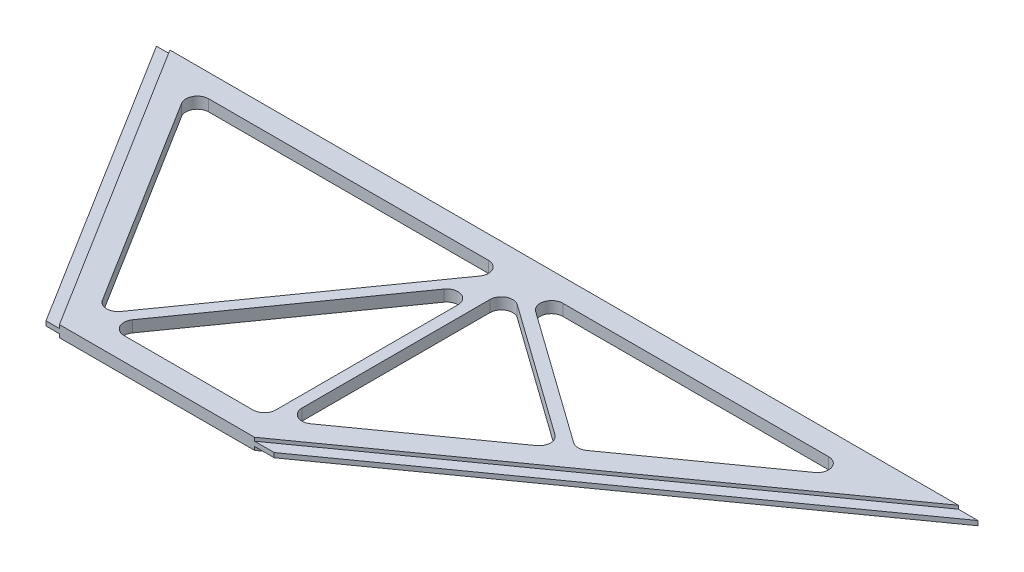
SolidWorks part; units mm, degrees
material "6061-T6 (SS)"
ref_plane "Front Plane" through (0, 0, 0) normal (0, 0, 1) x (1, 0, 0)
ref_plane "Top Plane" through (0, 0, 0) normal (0, 1, 0) x (1, 0, 0)
ref_plane "Right Plane" through (0, 0, 0) normal (1, 0, 0) x (0, 0, -1)
sketch "CS path" plane through (0, 0, 0) normal (0, 1, 0) x (1, 0, 0)
  line L0 (-228.6, 0) -> (228.6, 0)
  line L1 (0, 0) -> (-63.5, -163.068) construction
  line L2 (0, -163.068) -> (228.6, 0)
  line L6 (-127, -163.068) -> (0, -163.068)
  line L9 (-127, -163.068) -> (-228.6, 0) construction
  line L12 (-127, -163.068) -> (-228.6, 0)
  dimension "D1" = 457.2
  dimension "D2" = 127
  dimension "D3" = 163.068
  dimension "D4" = 228.6
extrude "Boss-Extrude1" add sketch "CS path" along normal blind 3.175 and the other way blind 3.175
sketch "Sketch1" plane through (0, 3.175, 0) normal (0, 1, 0) x (1, 0, 0)
  line L0 (-228.6, 0) -> (-127, -163.068)
  line L1 (0, -163.068) -> (228.6, 0)
  line L2 (-228.6, 0) -> (228.6, 0) construction
  line L3 (-127, -163.068) -> (0, -163.068) construction
  line L4 (-221.1183, 0) -> (-119.5183, -163.068)
  line L5 (-10.9346, -163.068) -> (217.6654, 0)
  line L6 (-223.2105, 3.3579) -> (-121.6105, -159.7101) construction
  line L7 (-3.6876, -157.8985) -> (224.9124, 5.1695) construction
  line L8 (-228.6, 0) -> (-221.1183, 0)
  line L9 (-127, -163.068) -> (-119.5183, -163.068)
  line L10 (0, -163.068) -> (-10.9346, -163.068)
  line L11 (217.6654, 0) -> (228.6, 0)
  dimension "D1" = 6.35
extrude "Cut-Extrude1" cut sketch "Sketch1" against normal blind 1.905
mirror "Mirror1" about plane through (0, 0, 0) normal (0, 1, 0) of "Cut-Extrude1"
sketch "Sketch2" plane through (0, 3.175, 0) normal (0, 1, 0) x (1, 0, 0)
  line L0 (-221.1183, 0) -> (217.6654, 0) construction
  line L1 (217.6654, 0) -> (-10.9346, -163.068) construction
  line L2 (-10.9346, -163.068) -> (-119.5183, -163.068) construction
  line L3 (-119.5183, -163.068) -> (-221.1183, 0) construction
  line L4 (-198.2422, -12.7) -> (177.9924, -12.7)
  line L5 (177.9924, -12.7) -> (-15.0001, -150.368)
  line L6 (-15.0001, -150.368) -> (-112.4677, -150.368)
  line L7 (-112.4677, -150.368) -> (-198.2422, -12.7)
  line L8 (-15.0001, -150.368) -> (-15.0001, -12.7) construction
  line L9 (-15.0001, -12.7) -> (-112.4677, -150.368) construction
  line L10 (-15.0001, -12.7) -> (81.4962, -81.534) construction
  line L11 (-15.0001, -150.368) -> (-198.2422, -12.7) construction
  dimension "D1" = 12.7
extrude "Cut-Extrude2" cut sketch "Sketch2" against normal blind 6.35
sketch "Sketch3" plane through (0, 3.175, 0) normal (0, 1, 0) x (1, 0, 0)
  line L0 (-15.0001, -150.368) -> (-15.0001, -12.7) construction
  line L1 (177.9924, -12.7) -> (-198.2422, -12.7) construction
  line L2 (-15.0001, -12.7) -> (81.4962, -81.534) construction
  line L3 (-15.0001, -150.368) -> (177.9924, -12.7) construction
  line L4 (-15.0001, -12.7) -> (-112.4677, -150.368) construction
  line L5 (-18.8903, -12.7) -> (-114.2887, -147.4453)
  line L6 (-11.8251, -148.1032) -> (-11.8251, -18.8648)
  line L7 (-18.8903, -12.7) -> (-9.5328, -12.7)
  line L8 (-18.1751, -22.6792) -> (-108.5776, -150.368)
  line L9 (-18.1751, -150.368) -> (-18.1751, -22.6792)
  line L10 (-9.5328, -12.7) -> (84.2298, -79.584)
  line L11 (-198.2422, -12.7) -> (-112.4677, -150.368) construction
  line L12 (-112.4677, -150.368) -> (-15.0001, -150.368) construction
  line L13 (-15.0001, -150.368) -> (84.2298, -79.584) construction
  line L14 (177.9924, -12.7) -> (-198.2422, -12.7) construction
  line L15 (-17.5914, -10.8654) -> (-115.059, -148.5334) construction
  line L16 (78.7625, -83.484) -> (84.2298, -79.584)
  line L17 (-11.8251, -150.368) -> (-11.8251, -12.7) construction
  line L18 (-11.8251, -148.1032) -> (-15.0001, -150.368)
  line L19 (-13.1563, -10.1152) -> (83.34, -78.9492) construction
  line L20 (-15.0001, -150.368) -> (-18.1751, -150.368)
  line L21 (-11.8251, -18.8648) -> (78.7625, -83.484)
  line L22 (-114.2887, -147.4453) -> (-112.4677, -150.368)
  line L23 (-18.1751, -150.368) -> (-18.1751, -12.7) construction
  line L24 (-112.4677, -150.368) -> (-108.5776, -150.368)
  dimension "D1" = 3.175
  dimension "D2" = 3.175
extrude "Boss-Extrude2" add sketch "Sketch3" against normal blind 6.35
fillet "Fillet1" radius 6.35 10 edges at (84.2298, 0, 79.584) (-114.2887, 0, 147.4453) (-108.5776, 0, 150.368) (-18.1751, 0, 150.368) (-11.8251, 0, 148.1032) (78.7625, 0, 83.484) (-9.5328, 0, 12.7) (-18.8903, 0, 12.7) (-18.1751, 0, 22.6792) (-11.8251, 0, 18.8648)
fillet "Fillet2" radius 6.35 2 edges at (177.9924, 0, 12.7) (-198.2422, 0, 12.7)
